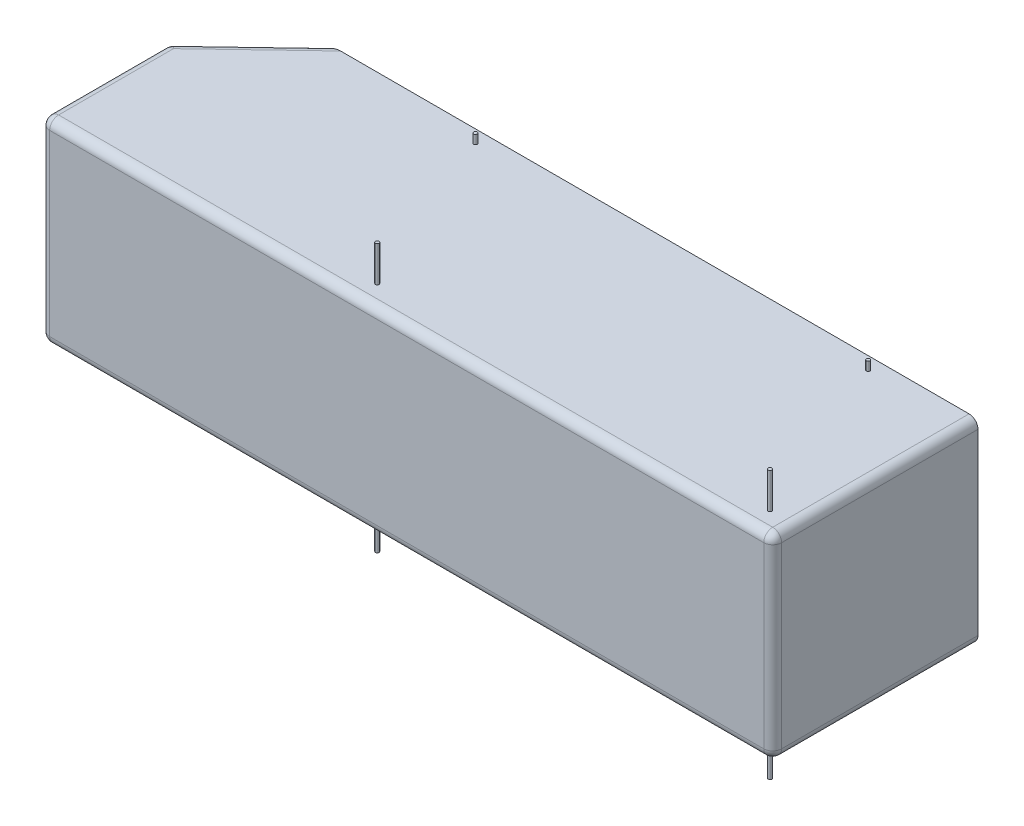
SolidWorks part; units mm, degrees
ref_plane "Front Plane" through (0, 0, 0) normal (0, 0, 1) x (1, 0, 0)
ref_plane "Top Plane" through (0, 0, 0) normal (0, 1, 0) x (1, 0, 0)
ref_plane "Right Plane" through (0, 0, 0) normal (1, 0, 0) x (0, 0, -1)
sketch "Sketch1" plane through (0, 0, 0) normal (0, 0, 1) x (1, 0, 0)
  line L3 (400, 110) -> (-400, 110)
  line L4 (410, 100) -> (410, -100)
  line L5 (400, -110) -> (-400, -110)
  line L6 (-410, 100) -> (-410, -100)
  line L7 (410, 110) -> (-410, -110) construction
  line L8 (410, -110) -> (-410, 110) construction
  arc A2 (-400, -110) -> (-410, -100) centre (-400, -100) cw
  arc A3 (-400, 110) -> (-410, 100) centre (-400, 100) ccw
  arc A4 (410, 100) -> (400, 110) centre (400, 100) ccw
  arc A5 (400, -110) -> (410, -100) centre (400, -100) ccw
  point P0 (0, 0)
  dimension "D1" = 10
  dimension "D2" = 10
  dimension "D3" = 10
  dimension "D4" = 10
  dimension "D5" = 800
  dimension "D6" = 200
extrude "Boss-Extrude1" add sketch "Sketch1" along normal blind 230
fillet "Fillet1" radius 10 8 edges at (-407.0711, -107.0711, 230) (-410, 0, 230) (-407.0711, 107.0711, 230) (0, 110, 230) (407.0711, 107.0711, 230) (410, 0, 230) (407.0711, -107.0711, 230) (0, -110, 230)
sketch "Sketch2" plane through (0, -110, 0) normal (0, -1, 0) x (1, 0, 0)
  line L0 (400, 220) -> (-400, 220) construction
  line L1 (-400, 220) -> (-400, 0) construction
  line L2 (400, 220) -> (400, 0) construction
  line L3 (220, 205) -> (220, 14) construction
  line L4 (220, 14) -> (301, 14) construction
  line L5 (-220, 205) -> (-220, 14) construction
  line L6 (-220, 14) -> (-139, 14) construction
  line L7 (-220, 205) -> (-58, 205) construction
  line L8 (220, 205) -> (382, 205) construction
  circle A0 centre (-220, 205) radius 2 construction
  circle A1 centre (220, 205) radius 2 construction
  circle A2 centre (301, 14) radius 2
  circle A3 centre (-139, 14) radius 2
  circle A4 centre (-58, 205) radius 2
  circle A5 centre (382, 205) radius 2
  dimension "D1" = 4
  dimension "D4" = 4
  dimension "D8" = 4
  dimension "D9" = 4
  dimension "D10" = 4
  dimension "D13" = 4
  dimension "D2" = 15
  dimension "D3" = 180
  dimension "D5" = 15
  dimension "D6" = 180
  dimension "D7" = 81
  dimension "D11" = 162
  dimension "D12" = 162
extrude "Boss-Extrude2" add sketch "Sketch2" along normal blind 40
sketch "Sketch3" plane through (0, 110, 0) normal (0, 1, 0) x (1, 0, 0)
  line L0 (-400, -220) -> (400, -220) construction
  line L1 (220, -205) -> (220, -14) construction
  line L2 (-400, -220) -> (-400, 0) construction
  line L3 (400, -220) -> (400, 0) construction
  line L4 (220, -14) -> (301, -14) construction
  line L5 (-220, -205) -> (-220, -14) construction
  line L6 (-220, -14) -> (-139, -14) construction
  line L7 (220, -205) -> (382, -205) construction
  line L8 (-220, -205) -> (-58, -205) construction
  circle A0 centre (-220, -205) radius 2 construction
  circle A1 centre (220, -205) radius 2 construction
  circle A2 centre (301, -14) radius 2
  circle A3 centre (-139, -14) radius 2
  circle A4 centre (382, -205) radius 2
  circle A5 centre (-58, -205) radius 2
  dimension "D1" = 4
  dimension "D4" = 4
  dimension "D7" = 4
  dimension "D8" = 4
  dimension "D10" = 4
  dimension "D12" = 4
  dimension "D2" = 15
  dimension "D3" = 180
  dimension "D5" = 15
  dimension "D6" = 180
  dimension "D9" = 162
  dimension "D11" = 162
extrude "Boss-Extrude3" add sketch "Sketch3" along normal blind 40
sketch "Sketch5" plane through (0, -110, 0) normal (0, -1, 0) x (1, 0, 0)
  line L5 (-318.5527, 0) -> (-432.2204, 108.2369)
  line L6 (-400, 0) -> (400, 0) construction
  line L7 (-432.2204, 108.2369) -> (-432.2204, 0)
  line L8 (-432.2204, 0) -> (-318.5527, 0)
extrude "Cut-Extrude2" cut sketch "Sketch5" against normal blind 300
fillet "Fillet2" radius 10 5 edges at (-359.2764, 110, 38.7779) (-407.0711, 107.0711, 84.2891) (-410, 0, 87.0781) (-407.0711, -107.0711, 84.2891) (-359.2764, -110, 38.7779)
sketch "Sketch8" plane through (0, -150, 0) normal (0, -1, 0) x (1, 0, 0)
  circle A0 centre (-139, 14) radius 2
extrude "Cut-Extrude3" cut sketch "Sketch8" against normal blind 30
sketch "Sketch9" plane through (0, -150, 0) normal (0, -1, 0) x (1, 0, 0)
  circle A0 centre (301, 14) radius 2
extrude "Cut-Extrude4" cut sketch "Sketch9" against normal blind 30
sketch "Sketch10" plane through (0, 150, 0) normal (0, 1, 0) x (1, 0, 0)
  circle A0 centre (301, -14) radius 2.6462
extrude "Cut-Extrude5" cut sketch "Sketch10" against normal blind 30
sketch "Sketch11" plane through (0, 150, 0) normal (0, 1, 0) x (1, 0, 0)
  circle A0 centre (-139, -14) radius 7.4287
extrude "Cut-Extrude6" cut sketch "Sketch11" against normal blind 30
